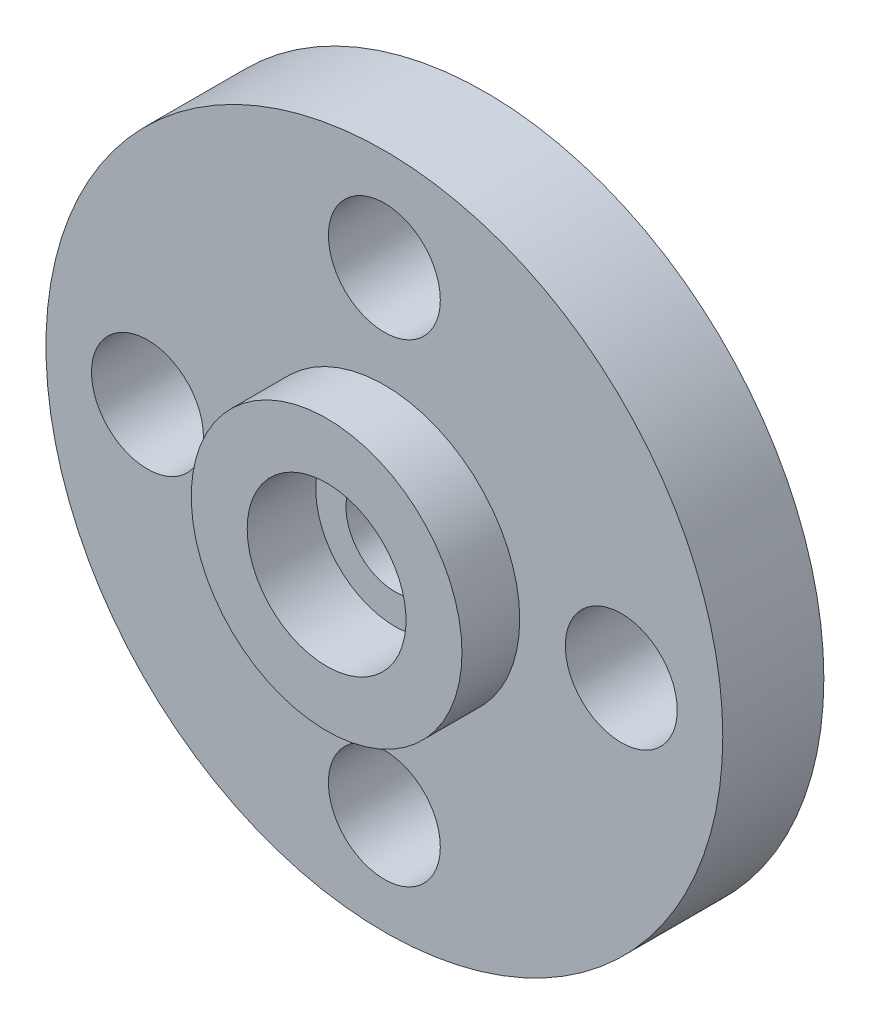
SolidWorks part; units mm, degrees
material "AISI 316 Annealed Stainless Steel Bar (SS)"
ref_plane "Front Plane" through (0, 0, 0) normal (0, 0, 1) x (1, 0, 0)
ref_plane "Top Plane" through (0, 0, 0) normal (0, 1, 0) x (1, 0, 0)
ref_plane "Right Plane" through (0, 0, 0) normal (1, 0, 0) x (0, 0, -1)
ref_axis "Axis1" through (0, 0, -1.1112) along (0, 0, 1)
sketch "Sketch1" plane through (0, 0, 0) normal (0, 0, 1) x (1, 0, 0)
  line L1 (0, 0) -> (0, 47.625) construction
  circle A0 centre (0, 0) radius 47.625
  circle A1 centre (0, 0) radius 33.3375 construction
  circle A2 centre (0, 33.3375) radius 7.874
  circle A6 centre (0, 0) radius 17.526
  circle A7 centre (0, 0) radius 19.05
  dimension "Flange OD" = 95.25
  dimension "Bolt Circle" = 66.675
  dimension "Bolt Hole Size" = 15.748
  dimension "Raised Face Dia." = 35.052
  dimension "Hub Dia." = 38.1
sketch "Sketch2" plane through (0, 0, 0) normal (1, 0, 0) x (0, 0, -1)
  line L0 (0, 0) -> (-6.35, 0) construction
  line L1 (-6.35, 0) -> (-20.574, 0) construction
  line L2 (-20.574, 0) -> (-28.702, 0) construction
  point P3 (-19.05, 0)
  dimension "Raised Face Height" = 6.35
  dimension "Thickness" = 20.574
  dimension "Lenght Through Hub" = 28.702
  dimension "D" = 9.652
extrude "Extrude1" add sketch "Sketch1" along normal up to vertex (6.35 mm away) contours A6 up to point (0, 0, 6.35)
extrude "Extrude2" add sketch "Sketch1<3>" along normal up to vertex (20.574 mm away) from vertex contours A0 up to point (0, 0, 20.574) starting at point (0, 0, 6.35)
sketch "Sketch1<3>" plane through (0, 0, 0) normal (0, 0, 1) x (1, 0, 0) same geometry as "Sketch1"
extrude "Extrude3" add sketch "Sketch1<4>" along normal up to vertex (28.702 mm away) from vertex contours A7 up to point (0, 0, 28.702) starting at point (0, 0, 20.574)
sketch "Sketch1<4>" plane through (0, 0, 0) normal (0, 0, 1) x (1, 0, 0) same geometry as "Sketch1"
extrude "Extrude4" cut sketch "Sketch1<5>" along normal up to surface (20.574 mm away) from surface contours A2 up to face at (47.625, 0, 20.574) starting at face at (47.625, 0, 6.35)
sketch "Sketch1<5>" plane through (0, 0, 0) normal (0, 0, 1) x (1, 0, 0) same geometry as "Sketch1"
pattern_circular "CirPattern1" count 4 over 360 about axis through (0, 0, -1.1112) along (0, 0, 1) of "Extrude4"
sketch "Sketch3" plane through (0, 0, 28.702) normal (0, 0, -1) x (-1, 0, 0)
  circle A0 centre (0, 0) radius 11.176
  circle A1 centre (0, 0) radius 6.9342
  dimension "Bore" = 22.352
  dimension "J" = 13.8684
extrude "Extrude5" cut sketch "Sketch3" along normal up to vertex (9.652 mm away) contours A0 up to point (0, 0, 19.05)
extrude "Extrude6" cut sketch "Sketch3<3>" along normal up to next contours A1
sketch "Sketch3<3>" plane through (0, 0, 28.702) normal (0, 0, -1) x (-1, 0, 0) same geometry as "Sketch3"
